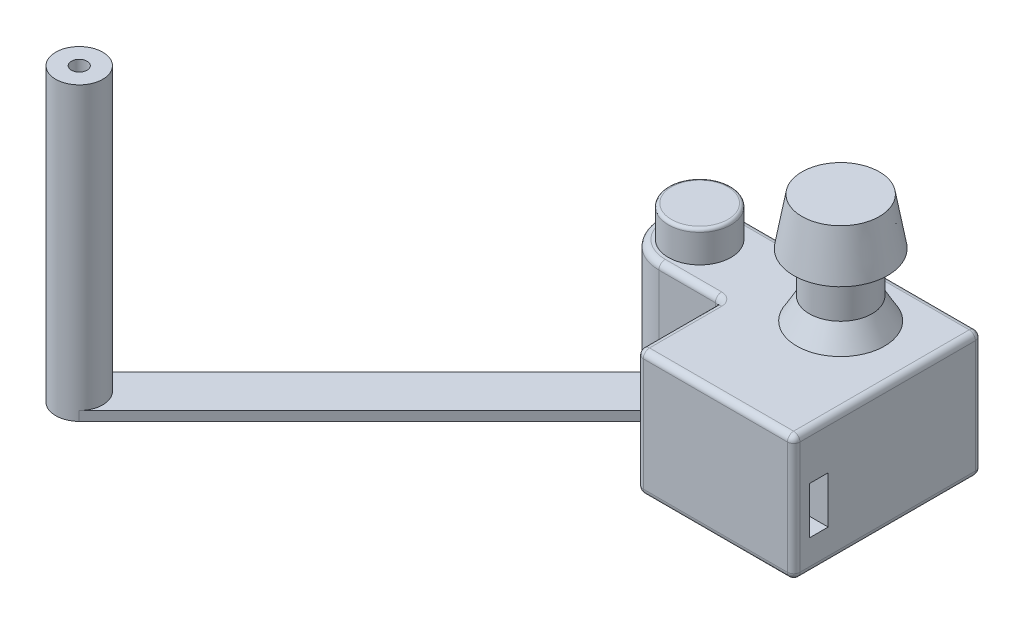
SolidWorks part; units mm, degrees
ref_plane "Front Plane" through (0, 0, 0) normal (0, 0, 1) x (1, 0, 0)
ref_plane "Top Plane" through (0, 0, 0) normal (0, 1, 0) x (1, 0, 0)
ref_plane "Right Plane" through (0, 0, 0) normal (1, 0, 0) x (0, 0, -1)
sketch "Sketch1" plane through (0, 0, 0) normal (0, 1, 0) x (1, 0, 0)
  circle A0 centre (0, 0) radius 10
  dimension "D1" = 20
extrude "Boss-Extrude1" add sketch "Sketch1" along normal blind 20
sketch "Sketch2" plane through (0, 0, 0) normal (0, -1, 0) x (1, 0, 0)
  line L0 (0, 0) -> (-41.2526, 0) construction
  line L1 (25, -20) -> (-25, -20)
  line L2 (25, -20) -> (25, 40)
  line L3 (25, 40) -> (-25, 40)
  line L4 (-25, -20) -> (-25, 40)
  circle A0 centre (0, 0) radius 10 construction
  dimension "D4" = 25
  dimension "D1" = 20
  dimension "D2" = 25
  dimension "D3" = 40
extrude "Boss-Extrude2" add sketch "Sketch2" along normal blind 40
sketch "Sketch3" plane through (0, 0, 0) normal (0, 1, 0) x (1, 0, 0)
  line L0 (0, 0) -> (-45, 0) construction
  line L1 (-25, -40) -> (-25, 20) construction
  line L2 (-45, -13) -> (-25, -13)
  line L3 (-25, -13) -> (-25, 13)
  line L4 (-25, 13) -> (-45, 13)
  circle A0 centre (-45, 0) radius 10
  arc A1 (-45, 13) -> (-45, -13) centre (-45, 0) ccw
  dimension "D1" = 20
  dimension "D3" = 3
  dimension "D2" = 20
extrude "Boss-Extrude3" add sketch "Sketch3" against normal blind 30
extrude "Boss-Extrude4" add sketch "Sketch3<2>" along normal blind 10 and the other way blind 30 contours A0 region at (-45, 0, 0)
sketch "Sketch3<2>" plane through (0, 0, 0) normal (0, 1, 0) x (1, 0, 0) same geometry as "Sketch3"
sketch "Sketch4" plane through (0, 20, 0) normal (0, 1, 0) x (1, 0, 0)
  circle A0 centre (0, 0) radius 15
  dimension "D1" = 30
extrude "Boss-Extrude5" add sketch "Sketch4" along normal blind 15 draft 10 separate body contours A0
sketch "Sketch6" plane through (-25, 0, 0) normal (-1, 0, 0) x (0, 0, 1)
  line L0 (40, -40) -> (40, 0) construction
  line L1 (29, -15) -> (35, -15)
  line L2 (29, -15) -> (29, -30)
  line L3 (29, -30) -> (35, -30)
  line L4 (35, -15) -> (35, -30)
  line L5 (13, -30) -> (-13, -30) construction
  point P6 (40, -20)
  dimension "D1" = 6
  dimension "D2" = 15
  dimension "D3" = 5
extrude "Cut-Extrude1" cut sketch "Sketch6" against normal blind 15
sketch "Sketch7" plane through (-10, 0, 0) normal (-1, 0, 0) x (0, 0, 1)
  line L0 (32, -15) -> (32, -30) construction
  line L1 (34.5, -15.5) -> (32.5, -15.5)
  line L2 (34.5, -15.5) -> (34.5, -29.5)
  line L3 (34.5, -29.5) -> (32.5, -29.5)
  line L4 (32.5, -15.5) -> (32.5, -29.5)
  line L5 (35, -15) -> (29, -15) construction
  line L6 (29, -30) -> (35, -30) construction
  line L7 (35, -30) -> (35, -15) construction
  line L8 (35, -15) -> (29, -15) construction
  line L9 (29, -30) -> (35, -30) construction
  dimension "D1" = 0.5
  dimension "D2" = 0.5
  dimension "D3" = 0.5
  dimension "D4" = 0.5
extrude "Boss-Extrude6" add sketch "Sketch7" along normal blind 12
chamfer "Chamfer1" distance 4 angle 60 1 edges at (0, 0, 10) first distance on face at (0, 0, 10)
fillet "Fillet1" radius 1 1 edges at (-45, 10, 10)
fillet "Fillet2" radius 2 6 edges at (25, -20, 40) (-25, -20, 40) (-25, -15, -13) (-25, -20, -20) (25, -20, -20) (-25, -15, 13)
fillet "Fillet3" radius 2 22 edges at (-24.4142, -40, 39.4142) (0, -40, 40) (24.4142, -40, 39.4142) (25, -40, 10) (24.4142, -40, -19.4142) (0, -40, -20) (-24.4142, -40, -19.4142) (-58, 0, 0) (-36, 0, -13) (-25.5858, 0, -13.5858) (-25, 0, -16.5) (-24.4142, 0, -19.4142) (0, 0, -20) (24.4142, 0, -19.4142) (25, 0, 10) (24.4142, 0, 39.4142) (0, 0, 40) (-24.4142, 0, 39.4142) (-25, 0, 26.5) (-25.5858, 0, 13.5858) (-25, -40, 10) (-36, 0, 13)
ref_plane "Plane2" through (0, 0, 0) normal (1, 0, 0) x (0, 0, -1)
mirror "Mirror1" about plane through (0, 0, 0) normal (1, 0, 0) of "Cut-Extrude1", "Boss-Extrude6"
sketch "Sketch8" plane through (0, -30, 0) normal (0, -1, 0) x (1, 0, 0)
  circle A0 centre (-45, 0) radius 7.5
  dimension "D1" = 15
extrude "Boss-Extrude7" add sketch "Sketch8" along normal blind 15 separate body
sketch "Sketch9" plane through (0, -45, 0) normal (0, -1, 0) x (1, 0, 0)
  line L0 (-50.3033, -5.3033) -> (-39.6967, 5.3033)
  line L5 (-50.3033, -5.3033) -> (-149.2983, 93.6916)
  line L6 (45, 0) -> (45, 7.5) construction
  line L7 (45, 0) -> (45, -7.5) construction
  line L8 (-39.6967, 5.3033) -> (-138.6916, 104.2983)
  line L9 (-149.2983, 93.6916) -> (-138.6916, 104.2983)
  line L10 (-45, 0) -> (-35.0549, 0) construction
  circle A3 centre (-45, 0) radius 7.5
  circle A4 centre (-45, 0) radius 7.5 construction
  circle A5 centre (-143.9949, 98.9949) radius 7.5
  dimension "D1" = 140
  dimension "D2" = 45
extrude "Boss-Extrude8" add sketch "Sketch9" against normal blind 3 contours A5 | L0 L5 L9 L8
sketch "Sketch10" plane through (0, -42, 0) normal (0, 1, 0) x (1, 0, 0)
  circle A0 centre (-143.9949, -98.9949) radius 7.5
  arc A1 (-149.2983, -93.6916) -> (-138.6916, -104.2983) centre (-143.9949, -98.9949) ccw construction
  point P4 (0, 0)
  point P5 (36.2064, -3.0418)
  point P6 (-75, -51.9615)
extrude "Boss-Extrude9" add sketch "Sketch10" along normal blind 90
ref_plane "Plane3" through (0, 27.5, 0) normal (0, 1, 0) x (1, 0, 0)
sketch "Sketch11" plane through (0, 27.5, 0) normal (0, 1, 0) x (1, 0, 0)
  line L0 (0, 0) -> (-12.3551, 0) construction
  line L1 (-12.3551, 0) -> (-15, 0) construction
  circle A0 centre (0, 0) radius 13.6775
  circle A1 centre (0, 0) radius 12.3551 construction
  circle A2 centre (0, 0) radius 15 construction
  point P8 (0, 0)
  point P12 (-13.6775, 0)
hole_wizard "M6 Tapped Hole1" positions "3DSketch1" profile "Sketch14" tap size "M6" standard "GB"
sketch3d "3DSketch1"
  line L0 (-143.9949, -42, 98.9949) -> (-143.9949, -45, 98.9949) construction
  point P0 (-143.9949, 48, 98.9949)
sketch "Sketch14" plane through (-143.9949, 48, 98.9949) normal (1, 0, 0) x (0, 0, 1)
  line L0 (0, 0) -> (0, 17.5022)
  line L1 (0, 17.5022) -> (2.5, 16)
  line L2 (2.5, 16) -> (2.5, 0)
  line L5 (2.5, 0) -> (0, 0)
  line L10 (0, 17.5022) -> (-2.5, 16) construction
  line L11 (0, -6.35) -> (0, 107.95) construction
  dimension "Tap Drill Dia." = 5
  dimension "Tap Drill Depth" = 16
  dimension "Drill Angle" = 118
cosmetic thread "Hole Thread1" parameters "D1"=13, "D2"=6
